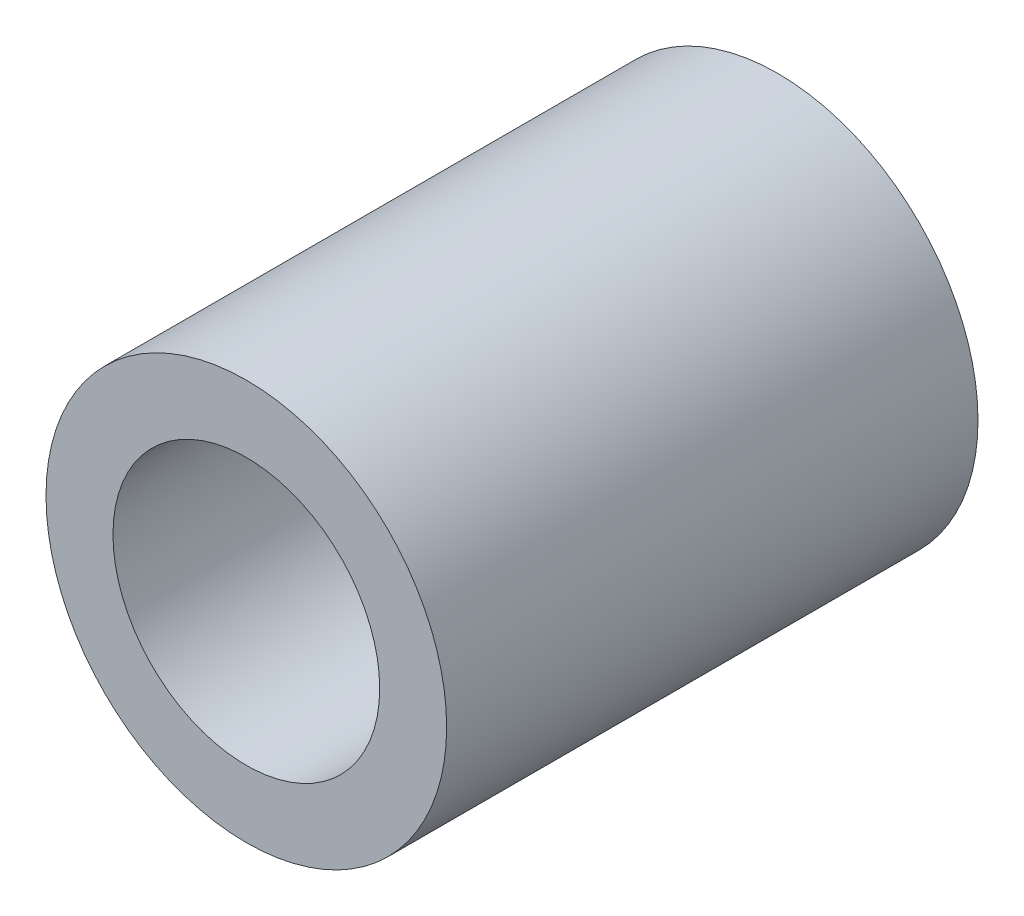
SolidWorks part; units mm, degrees
ref_plane "Front Plane" through (0, 0, 0) normal (0, 0, 1) x (1, 0, 0)
ref_plane "Top Plane" through (0, 0, 0) normal (0, 1, 0) x (1, 0, 0)
ref_plane "Right Plane" through (0, 0, 0) normal (1, 0, 0) x (0, 0, -1)
sketch "Sketch1" plane through (0, 0, 0) normal (0, 0, 1) x (1, 0, 0)
  circle A0 centre (0, 0) radius 2.394
  circle A1 centre (0, 0) radius 1.5939
  dimension "OD" = 4.7879
  dimension "ID" = 3.1877
sketch "Sketch2" plane through (0, 0, 0) normal (1, 0, 0) x (0, 0, -1)
  line L2 (3.175, 0) -> (-3.175, 0) construction
  line L4 (-3.175, -2.394) -> (-3.175, 2.3939) construction
  line L5 (-3.175, -1.5938) -> (3.175, -1.5938)
  line L6 (3.175, 1.5938) -> (-3.175, 1.5938)
  line L7 (3.175, -2.394) -> (3.175, 2.3939) construction
  line L8 (-3.175, 2.3939) -> (3.175, 2.3939) construction
  line L9 (-3.175, -2.394) -> (3.175, -2.394) construction
  line L10 (0, 2.394) -> (0, -2.394) construction
  line L11 (0, 1.5938) -> (0, -1.5938) construction
  point P4 (0, -1.5938)
  point P7 (0, 1.5938)
  point P8 (0, 0)
  point P12 (-3.175, 0)
  point P15 (3.175, 0)
  point P16 (0, -2.394)
  point P17 (0, 2.394)
  dimension "Length" = 6.35
sketch "Sketch5" plane through (0, 0, 0) normal (0, 0, 1) x (1, 0, 0)
  circle A1 centre (0, 0) radius 1.5939
  circle A2 centre (0, 0) radius 1.5939
  circle A3 centre (0, 0) radius 2.394
  circle A4 centre (0, 0) radius 2.394
  dimension "D1" = 0
  dimension "D2" = 0
extrude "Boss-Extrude1" add sketch "Sketch5" along normal up to vertex and the other way up to vertex up to point (0, 0, 3.175) other way up to point (0, 0, -3.175)
sketch "Sketch4" plane through (0, 0, 3.175) normal (0, 0, 1) x (1, 0, 0)
  line L0 (0, 0) -> (-1.127, 1.127)
  line L2 (0, -2.394) -> (0, 2.3939) construction
  circle A1 centre (0, 0) radius 1.5939 construction
  dimension "D1" = 45
equation "\"D1\"= \"Length@Sketch2\""
